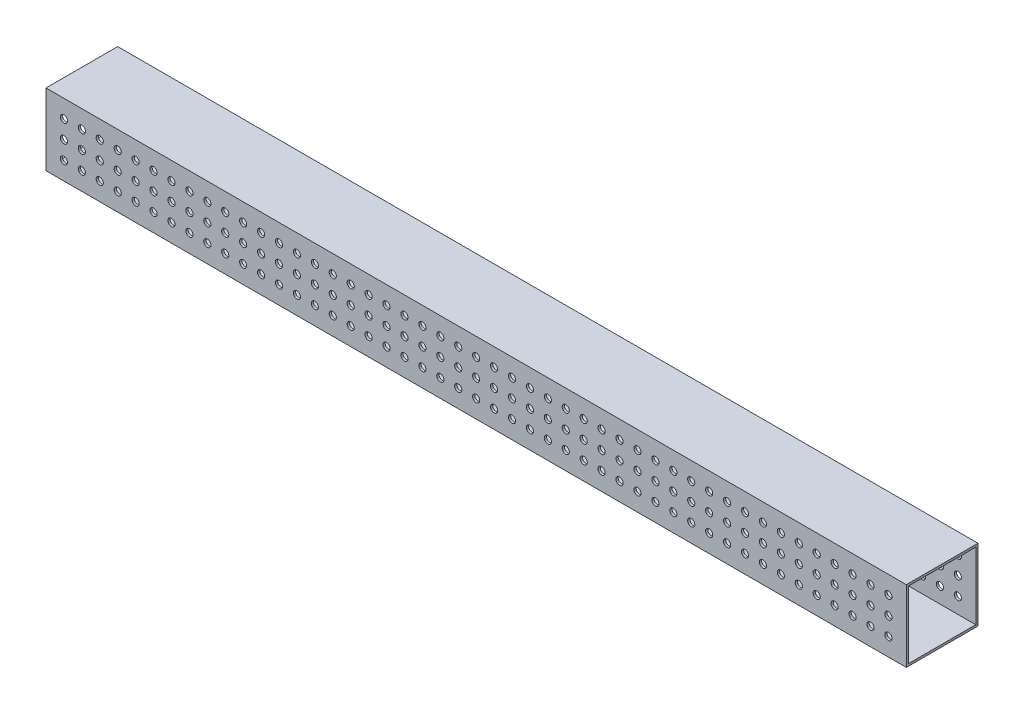
SolidWorks part; units mm, degrees
ref_plane "Front Plane" through (0, 0, 0) normal (0, 0, 1) x (1, 0, 0)
ref_plane "Top Plane" through (0, 0, 0) normal (0, 1, 0) x (1, 0, 0)
ref_plane "Right Plane" through (0, 0, 0) normal (1, 0, 0) x (0, 0, -1)
sketch "Sketch1" plane through (0, 0, 0) normal (1, 0, 0) x (0, 0, -1)
  line L1 (-25.4, -25.4) -> (25.4, -25.4)
  line L2 (-25.4, -25.4) -> (-25.4, 25.4)
  line L3 (-25.4, 25.4) -> (25.4, 25.4)
  line L4 (25.4, -25.4) -> (25.4, 25.4)
  line L5 (-25.4, -25.4) -> (25.4, 25.4) construction
  line L6 (-25.4, 25.4) -> (25.4, -25.4) construction
  line L7 (-23.8125, -23.8125) -> (23.8125, -23.8125)
  line L8 (-23.8125, -23.8125) -> (-23.8125, 23.8125)
  line L9 (-23.8125, 23.8125) -> (23.8125, 23.8125)
  line L10 (23.8125, -23.8125) -> (23.8125, 23.8125)
  line L11 (-23.8125, -23.8125) -> (23.8125, 23.8125) construction
  line L12 (-23.8125, 23.8125) -> (23.8125, -23.8125) construction
  point P0 (0, 0)
  point P7 (0, 0)
  dimension "D1" = 50.8
  dimension "D2" = 50.8
  dimension "D3" = 47.625
extrude "Boss-Extrude1" add sketch "Sketch1" along normal blind 609.6
sketch "Sketch2" plane through (0, 0, 25.4) normal (0, 0, 1) x (1, 0, 0)
  line L0 (-1000, 0) -> (49000, 0) construction
  line L2 (-994.1549, 12.7) -> (49005.8451, 12.7) construction
  line L3 (-984.8446, -12.7) -> (49015.1554, -12.7) construction
  line L4 (609.6, 25.4) -> (0, 25.4) construction
  line L5 (609.6, -25.4) -> (0, -25.4) construction
  line L6 (0, 25.4) -> (0, -25.4) construction
  line L7 (12.7, 12.7) -> (12.7, 0) construction
  line L8 (12.7, 12.7) -> (25.4, 12.7) construction
  circle A24 centre (12.7, 12.7) radius 2.54
  circle A25 centre (12.7, 0) radius 2.54
  circle A26 centre (12.7, -12.7) radius 2.54
  circle A27 centre (25.4, 12.7) radius 2.54
  circle A28 centre (25.4, 0) radius 2.54
  circle A29 centre (25.4, -12.7) radius 2.54
  circle A30 centre (38.1, 12.7) radius 2.54
  circle A31 centre (38.1, 0) radius 2.54
  circle A32 centre (38.1, -12.7) radius 2.54
  circle A33 centre (50.8, 12.7) radius 2.54
  circle A34 centre (50.8, 0) radius 2.54
  circle A35 centre (50.8, -12.7) radius 2.54
  circle A36 centre (63.5, 12.7) radius 2.54
  circle A37 centre (63.5, 0) radius 2.54
  circle A38 centre (63.5, -12.7) radius 2.54
  circle A39 centre (76.2, 12.7) radius 2.54
  circle A40 centre (76.2, 0) radius 2.54
  circle A41 centre (76.2, -12.7) radius 2.54
  circle A42 centre (88.9, 12.7) radius 2.54
  circle A43 centre (88.9, 0) radius 2.54
  circle A44 centre (88.9, -12.7) radius 2.54
  circle A45 centre (101.6, 12.7) radius 2.54
  circle A46 centre (101.6, 0) radius 2.54
  circle A47 centre (101.6, -12.7) radius 2.54
  circle A48 centre (114.3, 12.7) radius 2.54
  circle A49 centre (114.3, 0) radius 2.54
  circle A50 centre (114.3, -12.7) radius 2.54
  circle A51 centre (127, 12.7) radius 2.54
  circle A52 centre (127, 0) radius 2.54
  circle A53 centre (127, -12.7) radius 2.54
  circle A54 centre (139.7, 12.7) radius 2.54
  circle A55 centre (139.7, 0) radius 2.54
  circle A56 centre (139.7, -12.7) radius 2.54
  circle A57 centre (152.4, 12.7) radius 2.54
  circle A58 centre (152.4, 0) radius 2.54
  circle A59 centre (152.4, -12.7) radius 2.54
  circle A60 centre (165.1, 12.7) radius 2.54
  circle A61 centre (165.1, 0) radius 2.54
  circle A62 centre (165.1, -12.7) radius 2.54
  circle A63 centre (177.8, 12.7) radius 2.54
  circle A64 centre (177.8, 0) radius 2.54
  circle A65 centre (177.8, -12.7) radius 2.54
  circle A66 centre (190.5, 12.7) radius 2.54
  circle A67 centre (190.5, 0) radius 2.54
  circle A68 centre (190.5, -12.7) radius 2.54
  circle A69 centre (203.2, 12.7) radius 2.54
  circle A70 centre (203.2, 0) radius 2.54
  circle A71 centre (203.2, -12.7) radius 2.54
  circle A72 centre (215.9, 12.7) radius 2.54
  circle A73 centre (215.9, 0) radius 2.54
  circle A74 centre (215.9, -12.7) radius 2.54
  circle A75 centre (228.6, 12.7) radius 2.54
  circle A76 centre (228.6, 0) radius 2.54
  circle A77 centre (228.6, -12.7) radius 2.54
  circle A78 centre (241.3, 12.7) radius 2.54
  circle A79 centre (241.3, 0) radius 2.54
  circle A80 centre (241.3, -12.7) radius 2.54
  circle A81 centre (254, 12.7) radius 2.54
  circle A82 centre (254, 0) radius 2.54
  circle A83 centre (254, -12.7) radius 2.54
  circle A84 centre (266.7, 12.7) radius 2.54
  circle A85 centre (266.7, 0) radius 2.54
  circle A86 centre (266.7, -12.7) radius 2.54
  circle A87 centre (279.4, 12.7) radius 2.54
  circle A88 centre (279.4, 0) radius 2.54
  circle A89 centre (279.4, -12.7) radius 2.54
  circle A90 centre (292.1, 12.7) radius 2.54
  circle A91 centre (292.1, 0) radius 2.54
  circle A92 centre (292.1, -12.7) radius 2.54
  circle A93 centre (304.8, 12.7) radius 2.54
  circle A94 centre (304.8, 0) radius 2.54
  circle A95 centre (304.8, -12.7) radius 2.54
  circle A96 centre (317.5, 12.7) radius 2.54
  circle A97 centre (317.5, 0) radius 2.54
  circle A98 centre (317.5, -12.7) radius 2.54
  circle A99 centre (330.2, 12.7) radius 2.54
  circle A100 centre (330.2, 0) radius 2.54
  circle A101 centre (330.2, -12.7) radius 2.54
  circle A102 centre (342.9, 12.7) radius 2.54
  circle A103 centre (342.9, 0) radius 2.54
  circle A104 centre (342.9, -12.7) radius 2.54
  circle A105 centre (355.6, 12.7) radius 2.54
  circle A106 centre (355.6, 0) radius 2.54
  circle A107 centre (355.6, -12.7) radius 2.54
  circle A108 centre (368.3, 12.7) radius 2.54
  circle A109 centre (368.3, 0) radius 2.54
  circle A110 centre (368.3, -12.7) radius 2.54
  circle A111 centre (381, 12.7) radius 2.54
  circle A112 centre (381, 0) radius 2.54
  circle A113 centre (381, -12.7) radius 2.54
  circle A114 centre (393.7, 12.7) radius 2.54
  circle A115 centre (393.7, 0) radius 2.54
  circle A116 centre (393.7, -12.7) radius 2.54
  circle A117 centre (406.4, 12.7) radius 2.54
  circle A118 centre (406.4, 0) radius 2.54
  circle A119 centre (406.4, -12.7) radius 2.54
  circle A120 centre (419.1, 12.7) radius 2.54
  circle A121 centre (419.1, 0) radius 2.54
  circle A122 centre (419.1, -12.7) radius 2.54
  circle A123 centre (431.8, 12.7) radius 2.54
  circle A124 centre (431.8, 0) radius 2.54
  circle A125 centre (431.8, -12.7) radius 2.54
  circle A126 centre (444.5, 12.7) radius 2.54
  circle A127 centre (444.5, 0) radius 2.54
  circle A128 centre (444.5, -12.7) radius 2.54
  circle A129 centre (457.2, 12.7) radius 2.54
  circle A130 centre (457.2, 0) radius 2.54
  circle A131 centre (457.2, -12.7) radius 2.54
  circle A132 centre (469.9, 12.7) radius 2.54
  circle A133 centre (469.9, 0) radius 2.54
  circle A134 centre (469.9, -12.7) radius 2.54
  circle A135 centre (482.6, 12.7) radius 2.54
  circle A136 centre (482.6, 0) radius 2.54
  circle A137 centre (482.6, -12.7) radius 2.54
  circle A138 centre (495.3, 12.7) radius 2.54
  circle A139 centre (495.3, 0) radius 2.54
  circle A140 centre (495.3, -12.7) radius 2.54
  circle A141 centre (508, 12.7) radius 2.54
  circle A142 centre (508, 0) radius 2.54
  circle A143 centre (508, -12.7) radius 2.54
  circle A144 centre (520.7, 12.7) radius 2.54
  circle A145 centre (520.7, 0) radius 2.54
  circle A146 centre (520.7, -12.7) radius 2.54
  circle A147 centre (533.4, 12.7) radius 2.54
  circle A148 centre (533.4, 0) radius 2.54
  circle A149 centre (533.4, -12.7) radius 2.54
  circle A150 centre (546.1, 12.7) radius 2.54
  circle A151 centre (546.1, 0) radius 2.54
  circle A152 centre (546.1, -12.7) radius 2.54
  circle A153 centre (558.8, 12.7) radius 2.54
  circle A154 centre (558.8, 0) radius 2.54
  circle A155 centre (558.8, -12.7) radius 2.54
  circle A156 centre (571.5, 12.7) radius 2.54
  circle A157 centre (571.5, 0) radius 2.54
  circle A158 centre (571.5, -12.7) radius 2.54
  circle A159 centre (584.2, 12.7) radius 2.54
  circle A160 centre (584.2, 0) radius 2.54
  circle A161 centre (584.2, -12.7) radius 2.54
  circle A162 centre (596.9, 12.7) radius 2.54
  circle A163 centre (596.9, 0) radius 2.54
  circle A164 centre (596.9, -12.7) radius 2.54
  dimension "D1" = 12.7
  dimension "D3" = 5.08
  dimension "D2" = 12.7
  dimension "D4" = 12.7
  dimension "D6" = 12.7
  dimension "D8" = 12.7
  dimension "D5" = 3
  dimension "D7" = 47
extrude "Cut-Extrude2" cut sketch "Sketch2" against normal blind 609.6
